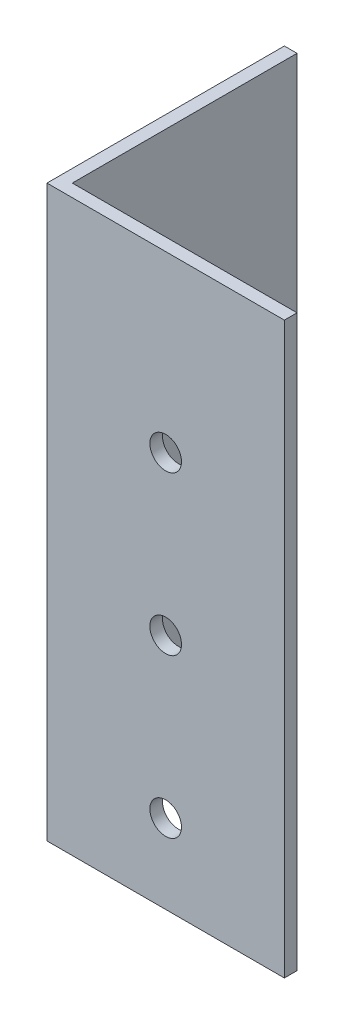
SolidWorks part; units mm, degrees
ref_plane "Спереди" through (0, 0, 0) normal (0, 0, 1) x (1, 0, 0)
ref_plane "Сверху" through (0, 0, 0) normal (0, 1, 0) x (1, 0, 0)
ref_plane "Справа" through (0, 0, 0) normal (1, 0, 0) x (0, 0, -1)
sketch "Эскиз1" plane through (0, 0, 0) normal (0, 1, 0) x (1, 0, 0)
  line L0 (0, 0) -> (75, 0)
  line L1 (0, 0) -> (0, 75)
extrude "Вытянуть-Тонкостенный1" add sketch "Эскиз1" along normal blind 180 thin thin type one direction wall 4
sketch "Эскиз6" plane through (0, 0, 0) normal (0, 0, -1) x (-1, 0, 0)
  circle A0 centre (-37.5, 25) radius 5
  circle A1 centre (-37.5, 75) radius 5
  circle A2 centre (-37.5, 125) radius 5
  dimension "D1" = 3
extrude "Вырез-Вытянуть1" cut sketch "Эскиз6" along normal blind 10
